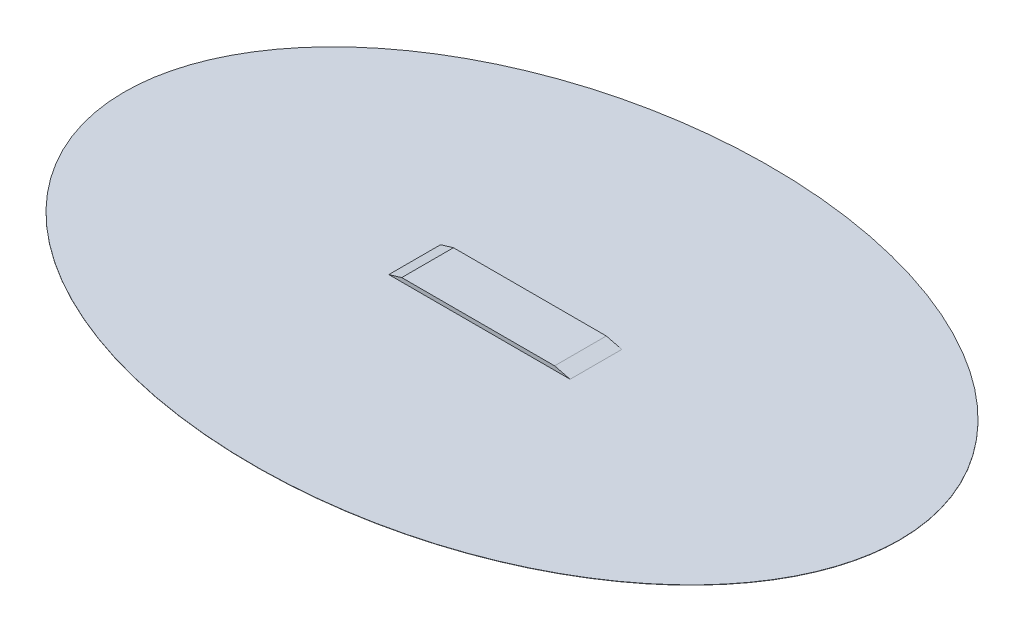
SolidWorks part; units mm, degrees
ref_plane "前视基准面" through (0, 0, 0) normal (0, 0, 1) x (1, 0, 0)
ref_plane "上视基准面" through (0, 0, 0) normal (0, 1, 0) x (1, 0, 0)
ref_plane "右视基准面" through (0, 0, 0) normal (1, 0, 0) x (0, 0, -1)
sketch "草图1" plane through (0, 0, 0) normal (0, 1, 0) x (1, 0, 0)
  ellipse E0 centre (0, 0) end of major axis (15000, 0) minor radius 10000
  dimension "D1" = 15000
  dimension "D2" = 10000
extrude "凸台-拉伸1" add sketch "草图1" along normal blind 10
sketch "草图4" plane through (0, 0, 0) normal (0, 0, 1) x (1, 0, 0)
  line L0 (-3765.6531, 10) -> (-3265.6531, 160)
  line L1 (15000, 10) -> (-15000, 10) construction
  line L2 (-3265.6531, 160) -> (2647.5806, 160)
  line L3 (2647.5806, 160) -> (3247.5806, 10)
  line L4 (3247.5806, 10) -> (-3765.6531, 10)
  point P5 (0, 0)
  point P8 (-2914.5466, 132.4332)
  point P9 (-3044.4659, 113.7441)
  dimension "D1" = 150
  dimension "D2" = 500
  dimension "D3" = 600
extrude "凸台-拉伸2" add sketch "草图4" along normal blind 1000 and the other way blind 1000
